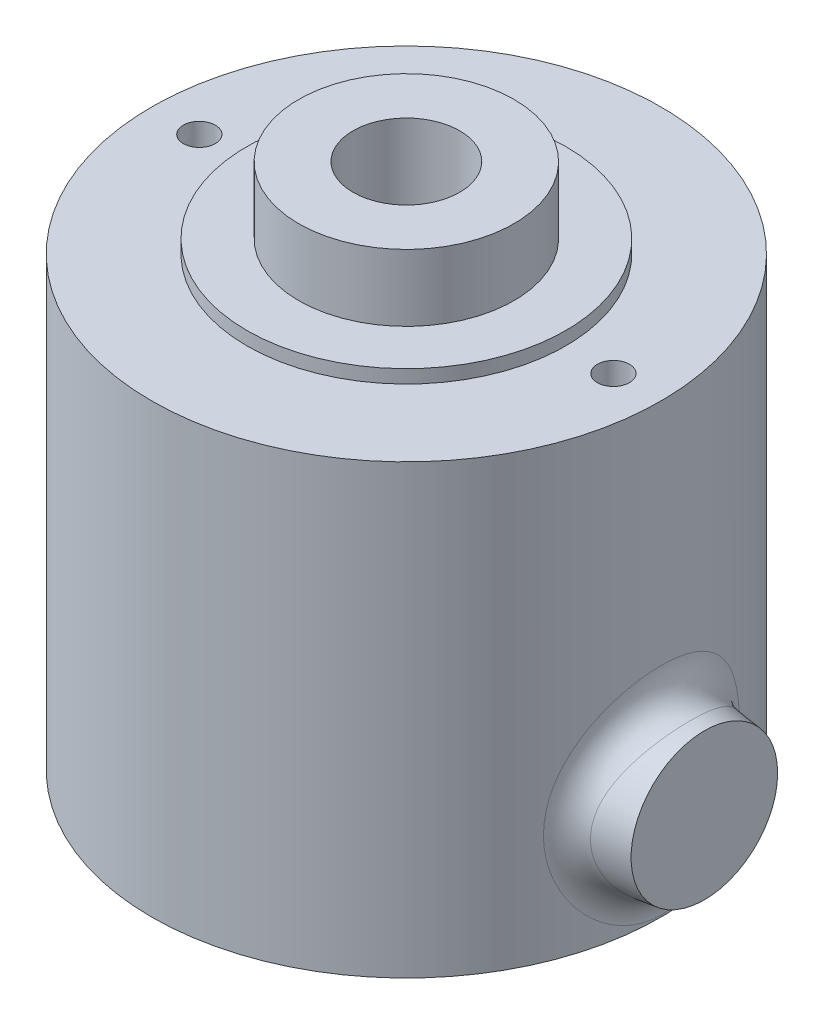
SolidWorks part; units mm, degrees
ref_plane "Front" through (0, 0, 0) normal (0, 0, 1) x (1, 0, 0)
ref_plane "Top" through (0, 0, 0) normal (0, 1, 0) x (1, 0, 0)
ref_plane "Right" through (0, 0, 0) normal (1, 0, 0) x (0, 0, -1)
sketch "Sketch2" plane through (0, 0, 0) normal (0, 1, 0) x (1, 0, 0)
  circle A0 centre (0, 0) radius 19.1
  dimension "D1" = 38.2
extrude "Boss-Extrude1" add sketch "Sketch2" along normal blind 33.53
sketch "Sketch3" plane through (0, 33.53, 0) normal (0, 1, 0) x (1, 0, 0)
  circle A0 centre (0, 0) radius 11.955
  circle A1 centre (0, 0) radius 8.075
  circle A2 centre (0, 0) radius 4
  dimension "D1" = 23.91
  dimension "D2" = 16.15
  dimension "D3" = 8
extrude "Boss-Extrude2" add sketch "Sketch3" along normal blind 1 contours A0 A1 region at (-11.6169, 33.53, 0)
extrude "Boss-Extrude3" add sketch "Sketch3<2>" along normal blind 6 contours A1 region at (-7.8466, 33.53, 0)
sketch "Sketch3<2>" plane through (0, 33.53, 0) normal (0, 1, 0) x (1, 0, 0) same geometry as "Sketch3"
sketch "Sketch4" plane through (0, 33.53, 0) normal (0, 1, 0) x (1, 0, 0)
  line L0 (-19.1, 0) -> (-11.955, 0) construction
  line L1 (11.955, 0) -> (19.1, 0) construction
  circle A0 centre (-15.5275, 0) radius 1.2
  circle A1 centre (15.5275, 0) radius 1.2
  circle A2 centre (0, 0) radius 19.1 construction
  circle A3 centre (0, 0) radius 11.955 construction
  circle A4 centre (0, 0) radius 19.1 construction
  circle A5 centre (0, 0) radius 11.955 construction
  point P22 (-15.5275, 0)
  point P24 (15.5275, 0)
  dimension "D1" = 2.4
extrude "Cut-Extrude1" cut sketch "Sketch4" against normal blind 6
sketch "Sketch5" plane through (0, 0, 0) normal (1, 0, 0) x (0, 0, -1)
  line L0 (0, 16.48) -> (0, 33.53) construction
  line L1 (19.1, 33.53) -> (-19.1, 33.53) construction
  circle A0 centre (0, 8.24) radius 8.24
  dimension "D1" = 17.05
extrude "Boss-Extrude4" add sketch "Sketch5" along normal blind 22.35 draft 7
fillet "Fillet1" radius 2.5 1 edges at (18.3902, 11.269, 5.1584)
